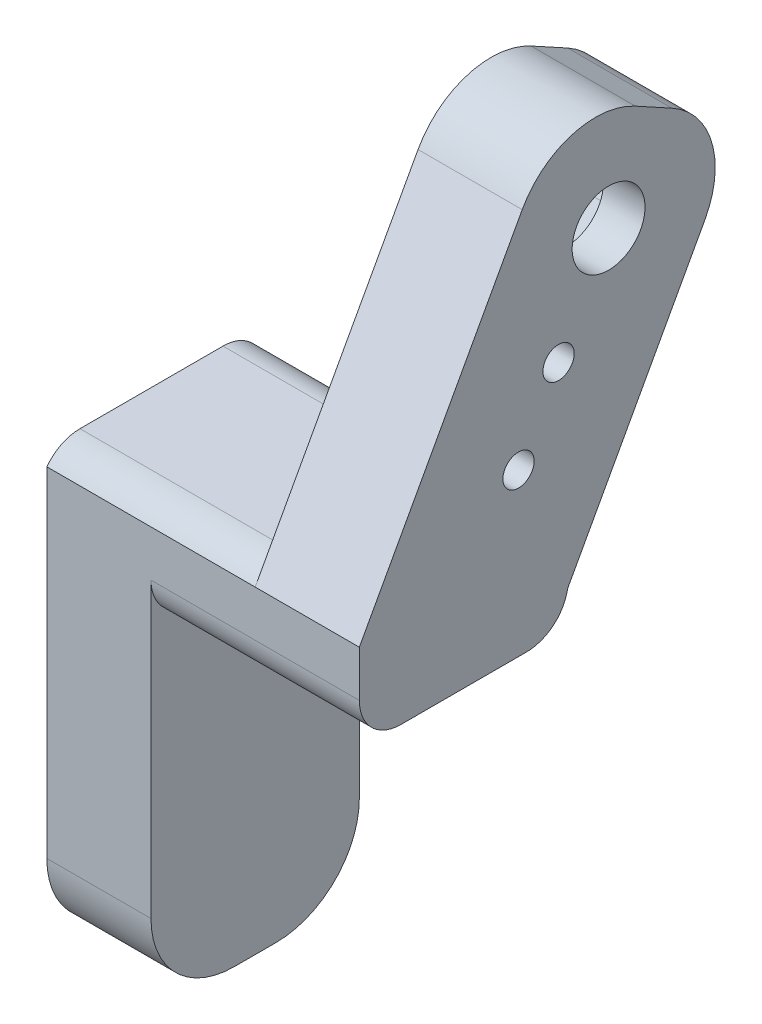
SolidWorks part; units mm, degrees
ref_plane "Front" through (0, 0, 0) normal (0, 0, 1) x (1, 0, 0)
ref_plane "Top" through (0, 0, 0) normal (0, 1, 0) x (1, 0, 0)
ref_plane "Right" through (0, 0, 0) normal (1, 0, 0) x (0, 0, -1)
sketch "Sketch3" plane through (0, 0, 0) normal (1, 0, 0) x (0, 0, -1)
  line L0 (0, 0) -> (-9.1244, -16.6657)
  line L3 (-9.1244, -16.6657) -> (-9.1244, -35.6657)
  dimension "D1" = 19
  dimension "D2" = 19
extrude "Extrude-Thin1" add sketch "Sketch3" along normal blind 15 thin thin type mid plane wall 10
sketch "Sketch4" plane through (0, 0, 14.1244) normal (0, 0, 1) x (1, 0, 0)
  line L0 (15, 2.4012) -> (10, 2.4012)
  line L1 (15, 2.4012) -> (0, 2.4012) construction
  line L2 (10, 2.4012) -> (10, -14.5988)
  line L3 (10, -14.5988) -> (0, -14.5988)
  line L4 (0, -14.5988) -> (0, -35.6657)
  line L5 (15, -35.6657) -> (0, -35.6657) construction
  line L6 (0, -35.6657) -> (5, -35.6657)
  line L7 (5, -35.6657) -> (5, -19.5988)
  line L8 (5, -19.5988) -> (15, -19.5988)
  line L9 (15, -15.3865) -> (15, -35.6657) construction
  line L10 (15, -19.5988) -> (15, 2.4012)
  dimension "D1" = 5
  dimension "D2" = 5
  dimension "D3" = 10
  dimension "D4" = 5
  dimension "D5" = 17
extrude "Cut-Extrude1" cut sketch "Sketch4" against normal through all flip side to cut
sketch "Sketch6" plane through (10, 0, 0) normal (-1, 0, 0) x (0, 0, 1)
  line L0 (0, 0) -> (13.9959, -25.5635) construction
  line L1 (13.6931, -14.5988) -> (4.3857, 2.4012) construction
  line L2 (-0.922, -6.082) -> (5.1503, -14.8513)
  line L3 (5.1503, -14.8513) -> (9.7369, -12.3401)
  line L4 (9.7369, -12.3401) -> (5.6205, -2.5)
  line L5 (-4.3857, -2.4012) -> (4.3857, 2.4012) construction
  arc A0 (5.6205, -2.5) -> (-0.922, -6.082) centre (2.161, -3.9471) ccw
  dimension "D1" = 7.5
  dimension "D2" = 11
  dimension "D3" = 4.5
  dimension "D4" = 12
extrude "Cut-Extrude2" cut sketch "Sketch6" against normal blind 3
sketch "Sketch7" plane through (13, 0, 0) normal (-1, 0, 0) x (0, 0, 1)
  line L0 (2.161, -3.9471) -> (7.8493, -14.3368) construction
  line L1 (13.6931, -14.5988) -> (4.3857, 2.4012) construction
  circle A0 centre (2.161, -3.9471) radius 1.75
  circle A1 centre (4.5622, -8.3328) radius 0.75
  circle A2 centre (6.4831, -11.8414) radius 0.75
  dimension "D1" = 3.5
  dimension "D2" = 1.5
  dimension "D3" = 4
  dimension "D4" = 5
extrude "Cut-Extrude3" cut sketch "Sketch7" against normal through all
fillet "Fillet1" radius 4 4 edges at (2.5, -35.6657, 14.1244) (2.5, -35.6657, 4.1244) (12.5, -2.4012, -4.3857) (12.5, 2.4012, 4.3857)
fillet "Fillet2" radius 2 2 edges at (10, -19.5988, 14.1244) (10, -19.5988, 4.1244)
fillet "Fillet3" radius 2 2 edges at (5, -14.5988, 2.2925) (5, -14.5988, 13.6931)
